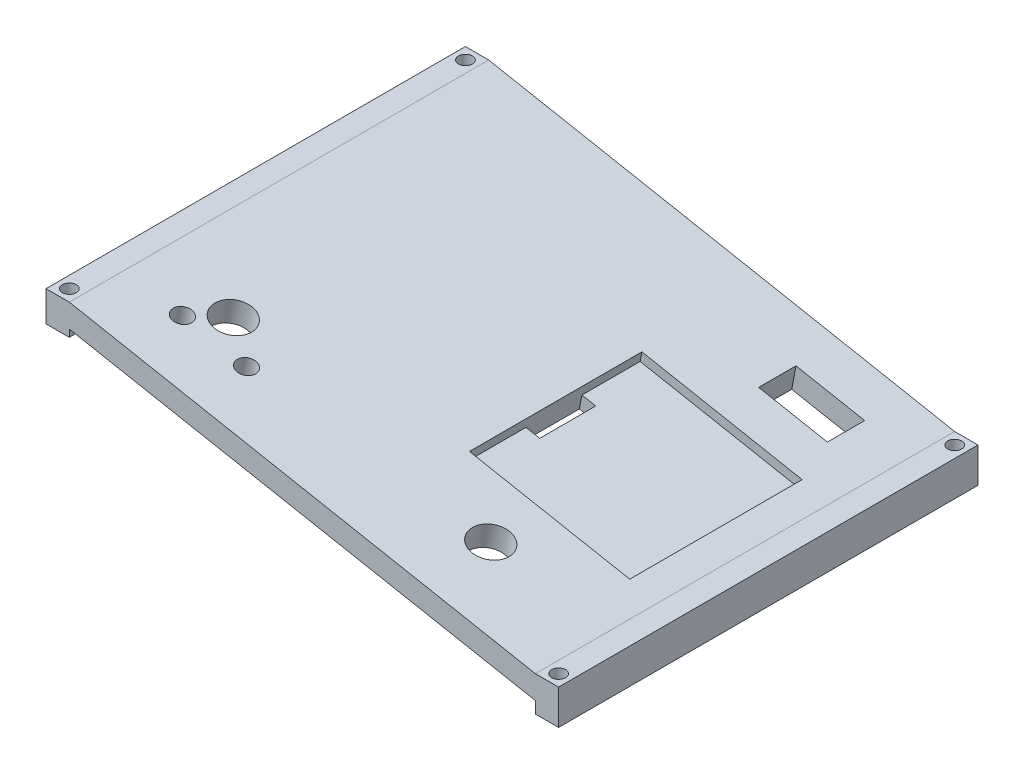
SolidWorks part; units mm, degrees
ref_plane "Front Plane" through (0, 0, 0) normal (0, 0, 1) x (1, 0, 0)
ref_plane "Top Plane" through (0, 0, 0) normal (0, 1, 0) x (1, 0, 0)
ref_plane "Right Plane" through (0, 0, 0) normal (1, 0, 0) x (0, 0, -1)
sketch "Sketch1" plane through (0, 0, 0) normal (0, 1, 0) x (1, 0, 0)
  line L1 (-55, -45) -> (55, -45)
  line L2 (-55, -45) -> (-55, 45)
  line L3 (-55, 45) -> (55, 45)
  line L4 (55, -45) -> (55, 45)
  line L5 (-55, -45) -> (55, 45) construction
  line L6 (-55, 45) -> (55, -45) construction
  point P0 (0, 0)
  dimension "D1" = 110
  dimension "D2" = 90
extrude "Boss-Extrude2" add sketch "Sketch1" along normal blind 27.5
sketch "Sketch4" plane through (0, 0, 45) normal (0, 0, 1) x (1, 0, 0)
  line L0 (-55, 27.5) -> (50, 7.5)
  line L1 (-55, 27.5) -> (-50, 27.5)
  line L2 (-55, 27.5) -> (-55, 20)
  line L3 (-55, 20) -> (-50, 20)
  line L4 (-50, 27.5) -> (-50, 20)
  line L5 (55, 0) -> (50, 0)
  line L6 (55, 0) -> (55, 7.5)
  line L7 (55, 7.5) -> (50, 7.5)
  line L8 (50, 0) -> (50, 7.5)
  line L9 (-55, 27.5) -> (-55, 22.5)
  line L10 (-55, 22.5) -> (50, 2.5)
  line L11 (50, 2.5) -> (50, 7.5)
  line L13 (-50, 26.5476) -> (-55, 26.5476)
  line L14 (-50, 26.5476) -> (-50, 27.5)
  line L15 (-50, 27.5) -> (-55, 27.5)
  line L16 (-55, 26.5476) -> (-55, 27.5)
  point P10 (-50, 26.5476)
  point P13 (-50, 21.5476)
  line M10 (-55, 0) -> (55, 0)
  line M11 (55, 0) -> (55, 27.5)
  line M12 (55, 27.5) -> (-55, 27.5)
  line M13 (-55, 27.5) -> (-55, 0)
  dimension "D1" = 7.5
  dimension "D2" = 5
  dimension "D3" = 7.5
  dimension "D4" = 5
  dimension "D5" = 5
  dimension "D6" = 5
extrude "Cut-Extrude5" cut sketch "Sketch4" against normal blind 90 contours L10 L4 L3 L8 M13 M10 | L7 L4 L0 M11 M12 | L4 L0 M12 | L13 L0 M13 region at (-51.6667, 27.1825, 45) region at (-53.3333, 26.8651, 45) region at (18.4059, 20.5297, 45) region at (-16.2188, 7.4789, 45)
sketch "Sketch5" plane through (0, 7.5, 0) normal (0, 1, 0) x (1, 0, 0)
  line L0 (50, 45) -> (50, -45) construction
  line L1 (55, 45) -> (50, 45)
  line L2 (55, 45) -> (55, 40)
  line L3 (55, 40) -> (50, 40)
  line L4 (50, 45) -> (50, 40)
  line L5 (55, 45) -> (50, 40) construction
  circle A0 centre (52.5, 42.5) radius 1.5
  dimension "D1" = 5
extrude "Cut-Extrude7" cut sketch "Sketch5" against normal blind 7.5 contours A0
sketch "Sketch7" plane through (0, 7.5, 0) normal (0, 1, 0) x (1, 0, 0)
  line L0 (50, 45) -> (50, -45) construction
  line L1 (55, -45) -> (50, -45)
  line L2 (55, -45) -> (55, -40)
  line L3 (55, -40) -> (50, -40)
  line L4 (50, -45) -> (50, -40)
  line L5 (55, -40) -> (50, -45) construction
  circle A0 centre (52.5, -42.5) radius 1.5
  dimension "D1" = 5
extrude "Cut-Extrude9" cut sketch "Sketch7" against normal blind 7.5 contours A0
sketch "Sketch9" plane through (0, 26.5476, 0) normal (0, 1, 0) x (1, 0, 0)
  line L0 (-50, 45) -> (-50, -45) construction
  line L1 (-55, 45) -> (-50, 45)
  line L2 (-55, 45) -> (-55, 40)
  line L3 (-55, 40) -> (-50, 40)
  line L4 (-50, 45) -> (-50, 40)
  line L5 (-50, 45) -> (-55, 40) construction
  circle A0 centre (-52.5, 42.5) radius 1.5
  dimension "D1" = 5
extrude "Cut-Extrude11" cut sketch "Sketch9" against normal blind 7.5 contours A0
sketch "Sketch12" plane through (0, 26.5476, 0) normal (0, 1, 0) x (1, 0, 0)
  line L0 (-50, 45) -> (-50, -45) construction
  line L1 (-55, -45) -> (-50, -45)
  line L2 (-55, -45) -> (-55, -40)
  line L3 (-55, -40) -> (-50, -40)
  line L4 (-50, -45) -> (-50, -40)
  line L5 (-55, -40) -> (-50, -45) construction
  circle A0 centre (-52.5, -42.5) radius 1.5
  dimension "D1" = 5
extrude "Cut-Extrude14" cut sketch "Sketch12" against normal blind 7.5 contours A0
sketch "Sketch18" plane through (3.1291, 16.4278, 0) normal (0.1871, 0.9823, 0) x (0.9823, -0.1871, 0)
  line L0 (47.7136, -45) -> (47.7136, 45) construction
  line L1 (6.3568, -6) -> (6.3568, 6)
  line L2 (9.3568, -6) -> (9.3568, 6)
  line L10 (6.3568, -6) -> (9.3568, -6)
  line L11 (6.3568, 6) -> (9.3568, 6)
  line L13 (6.3568, -18.5) -> (6.3568, 18.5)
  line L14 (6.3568, 18.5) -> (41.3568, 18.5)
  line L15 (41.3568, 18.5) -> (41.3568, -18.5)
  line L16 (41.3568, -18.5) -> (6.3568, -18.5)
  point P0 (-54.0843, -45)
  point P1 (47.7136, -45)
  point P3 (-54.0843, 45)
  point P4 (47.7136, 45)
  point P23 (6.3568, -18.5)
  point P26 (6.3568, 18.5)
  point P27 (6.3568, -6)
  point P28 (9.3568, -6)
  point P29 (9.3568, 6)
  point P30 (6.3568, 6)
  point P31 (41.3568, -18.5)
  point P32 (41.3568, 18.5)
  dimension "D1" = 37
  dimension "D2" = 35
  dimension "D3" = 12
  dimension "D4" = 3
extrude "Cut-Extrude22" cut sketch "Sketch18" against normal blind 2 contours L16 L15 L14 L13 L11 L2 L10 region at (27.014, 11.8783, 0)
extrude "Cut-Extrude23" cut sketch "Sketch18<5>" against normal blind 5 contours L11 L1 L10 L2 region at (10.8471, 14.9577, 0)
sketch "Sketch18<5>" plane through (3.1291, 16.4278, 0) normal (0.1871, 0.9823, 0) x (0.9823, -0.1871, 0) same geometry as "Sketch18"
sketch "Sketch23" plane through (3.1291, 16.4278, 0) normal (0.1871, 0.9823, 0) x (0.9823, -0.1871, 0)
  circle A0 centre (-41.5843, -33) radius 2
  circle A1 centre (-27.5843, -33) radius 2
  circle A2 centre (-36.5843, -27) radius 4
  point P5 (-34.0843, -25)
extrude "Cut-Extrude24" cut sketch "Sketch23" against normal blind 5
sketch "Sketch24" plane through (3.1291, 16.4278, 0) normal (0.1871, 0.9823, 0) x (0.9823, -0.1871, 0)
  line L2 (47.7136, -45) -> (47.7136, -30)
  circle A0 centre (22.7136, -30) radius 4
extrude "Cut-Extrude25" cut sketch "Sketch24" against normal blind 5 contours A0 region at (25.4415, 12.1778, 30)
sketch "Sketch25" plane through (3.1291, 16.4278, 0) normal (0.1871, 0.9823, 0) x (0.9823, -0.1871, 0)
  line L5 (22.7136, 27.5) -> (37.7136, 27.5)
  line L6 (22.7136, 27.5) -> (22.7136, 35.5)
  line L7 (22.7136, 35.5) -> (37.7136, 35.5)
  line L8 (37.7136, 27.5) -> (37.7136, 35.5)
extrude "Cut-Extrude26" cut sketch "Sketch25" against normal blind 5
